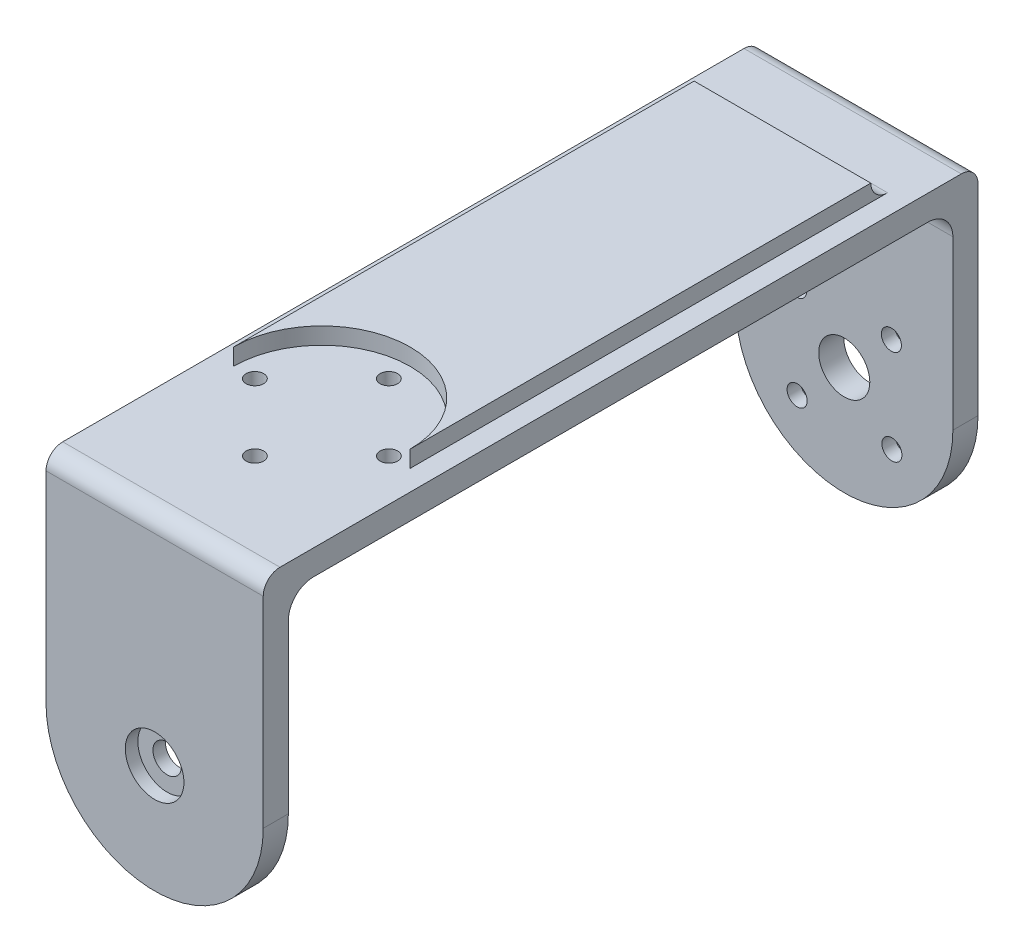
SolidWorks part; units mm, degrees
ref_plane "Plano frontal" through (0, 0, 0) normal (0, 0, 1) x (1, 0, 0)
ref_plane "Plano superior" through (0, 0, 0) normal (0, 1, 0) x (1, 0, 0)
ref_plane "Plano direito" through (0, 0, 0) normal (1, 0, 0) x (0, 0, -1)
sketch "Esboço1" plane through (0, 0, 0) normal (0, 0, 1) x (1, 0, 0)
  line L1 (10.97, 24.5719) -> (-10.97, 24.5719)
  line L3 (-10.97, 24.5719) -> (-12.97, 24.5719)
  line L6 (-12.97, 24.5719) -> (-12.97, -1.4281)
  line L7 (10.97, 24.5719) -> (12.97, 24.5719)
  line L8 (12.97, 24.5719) -> (12.97, -1.4281)
  line L9 (0, 24.5719) -> (0, -1.4281) construction
  arc A2 (-12.97, -1.4281) -> (12.97, -1.4281) centre (0, -1.4281) ccw
  circle A9 centre (0, -1.4281) radius 3.05 construction
  circle A10 centre (0, -1.4281) radius 3.05
  dimension "D1" = 26
  dimension "D2" = 2
  dimension "D3" = 2
extrude "Ressalto-extrusão1" add sketch "Esboço1" against normal blind 3
hole_wizard "Rebaixo para parafuso com cabeça redonda de M21" positions "Esboço10" profile "Esboço11" counterbore size "M2" standard "DIN" end condition up to next
sketch "Esboço10" plane through (0, 0, -3) normal (0, 0, -1) x (-1, 0, 0)
  circle A0 centre (-5.6247, 4.2606) radius 1.025 construction
  point P0 (-5.6247, 4.2606)
sketch "Esboço11" plane through (5.6247, 4.2606, -3) normal (1, 0, 0) x (0, 1, 0)
  line L0 (0, 0) -> (0, 3)
  line L1 (0, 3) -> (1.2, 3)
  line L3 (1.2, 3) -> (1.2, 1.4)
  line L4 (1.2, 1.4) -> (2.2, 1.4)
  line L5 (2.2, 1.4) -> (2.2, 0)
  line L7 (2.2, 0) -> (0, 0)
  line L11 (0, -6.35) -> (0, 107.95) construction
  dimension "Thru Hole Dia." = 2.4
  dimension "Thru Hole Depth" = 3
  dimension "C'Bore Dia." = 4.4
  dimension "C'Bore Depth" = 1.4
pattern_circular "PadrãoCircular1" count 4 over 360 about axis through (0, -1.4281, -3) along (0, 0, 1) of "Rebaixo para parafuso com cabeça redonda de M21"
sketch "Sketch6" plane through (0, 0, 0) normal (0, 0, 1) x (1, 0, 0)
  line L0 (-12.97, 24.5719) -> (-12.97, 21.5719)
  line L1 (-12.97, 24.5719) -> (-12.97, -1.4281) construction
  line L2 (-12.97, 21.5719) -> (12.97, 21.5719)
  line L3 (12.97, -1.4281) -> (12.97, 24.5719) construction
  line L4 (12.97, 21.5719) -> (12.97, 24.5719)
  line L5 (12.97, 24.5719) -> (-12.97, 24.5719)
  dimension "D1" = 3
extrude "Boss-Extrude2" add sketch "Sketch6" along normal blind 79.35
sketch "Sketch8" plane through (0, 0, 79.35) normal (0, 0, 1) x (1, 0, 0)
  line L0 (-12.97, 24.5719) -> (12.97, 24.5719)
  line L1 (12.97, 24.5719) -> (12.97, 21.5719)
  line L2 (12.97, 21.5719) -> (-12.97, 21.5719)
  line L3 (-12.97, 21.5719) -> (-12.97, 24.5719)
extrude "Boss-Extrude3" add sketch "Sketch8" along normal blind 3
sketch "Sketch9" plane through (0, 21.5719, 0) normal (0, -1, 0) x (1, 0, 0)
  line L0 (-12.97, 82.35) -> (-12.97, 79.35) construction
  line L1 (-12.97, 82.35) -> (-12.97, 0) construction
  line L2 (-12.97, 79.35) -> (-12.97, 0) construction
  line L3 (-12.97, 39.675) -> (12.97, 39.675) construction
  line L4 (12.97, 82.35) -> (12.97, 0) construction
  dimension "D1" = 3
ref_plane "Plane1" through (0, 0, 39.675) normal (0, 0, -1) x (-1, 0, 0)
mirror "Mirror1" about plane through (0, 0, 39.675) normal (0, 0, -1) of "Ressalto-extrusão1"
sketch "Sketch10" plane through (0, 0, 82.35) normal (0, 0, 1) x (1, 0, 0)
  circle A0 centre (0, -1.4281) radius 3.05
extrude "Boss-Extrude4" add sketch "Sketch10" against normal blind 3
sketch "Sketch12" plane through (0, 0, 82.35) normal (0, 0, 1) x (1, 0, 0)
  line L0 (0, 24.5719) -> (0, -1.4281) construction
  line L1 (12.97, 24.5719) -> (-12.97, 24.5719) construction
  circle A0 centre (0, -1.4281) radius 3.5
  dimension "D2" = 7
  dimension "D1" = 26
extrude "Cut-Extrude3" cut sketch "Sketch12" against normal blind 1.5
sketch "Sketch13" plane through (0, 0, 80.85) normal (0, 0, 1) x (1, 0, 0)
  circle A0 centre (0, -1.4281) radius 1.7
  dimension "D1" = 3.4
extrude "Cut-Extrude4" cut sketch "Sketch13" against normal blind 1.5
sketch "Sketch14" plane through (0, 24.5719, 0) normal (0, 1, 0) x (1, 0, 0)
  line L0 (12.97, -82.35) -> (12.97, -62.35) construction
  line L1 (12.97, 3) -> (12.97, -82.35) construction
  line L2 (12.97, -62.35) -> (-0.03, -62.35) construction
  line L3 (-10.58, -62.35) -> (-10.58, -7.35)
  line L4 (-10.58, -7.35) -> (10.52, -7.35)
  line L5 (10.52, -7.35) -> (10.52, -62.35)
  arc A0 (10.52, -62.35) -> (-10.58, -62.35) centre (-0.03, -62.35) ccw
  dimension "D1" = 21.1
  dimension "D2" = 20
  dimension "D3" = 55
  dimension "D4" = 13
extrude "Boss-Extrude5" add sketch "Sketch14" along normal blind 2
sketch "Sketch15" plane through (0, 24.5719, 0) normal (0, 1, 0) x (1, 0, 0)
  line L0 (-0.03, -62.35) -> (-0.03, -70.35) construction
  circle A1 centre (-0.03, -70.35) radius 1.05
  circle A2 centre (-8.03, -62.35) radius 1.05
  circle A3 centre (-0.03, -54.35) radius 1.05
  circle A4 centre (7.97, -62.35) radius 1.05
  point P14 (-0.03, -62.35)
  dimension "D2" = 2.1
  dimension "D3" = 4
extrude "Cut-Extrude5" cut sketch "Sketch15" against normal blind 3
fillet "Fillet2" radius 3 2 edges at (0, 21.5719, 0) (0, 21.5719, 79.35)
fillet "Filete3" radius 2 3 edges at (-0.03, 24.5719, 7.35) (0, 24.5719, 82.35) (0, 24.5719, -3)
